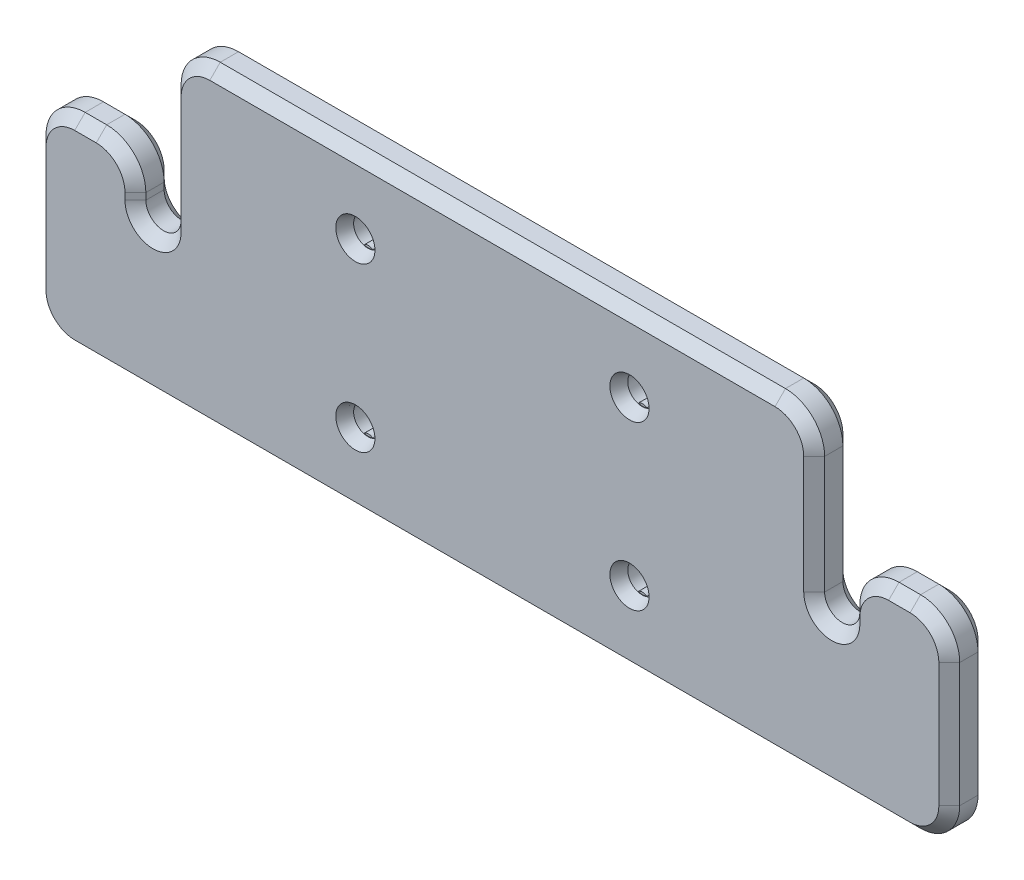
SolidWorks part; units mm, degrees
ref_plane "Front Plane" through (0, 0, 0) normal (0, 0, 1) x (1, 0, 0)
ref_plane "Top Plane" through (0, 0, 0) normal (0, 1, 0) x (1, 0, 0)
ref_plane "Right Plane" through (0, 0, 0) normal (1, 0, 0) x (0, 0, -1)
sketch "Sketch1" plane through (0, 0, 0) normal (0, 0, 1) x (1, 0, 0)
  line L0 (0, 12) -> (0, -12) construction
  line L1 (32, 12) -> (-32, 12)
  line L2 (35, 9) -> (35, -9)
  line L4 (-35, 9) -> (-35, -9)
  line L5 (10.5, 0) -> (-10.5, 0) construction
  line L6 (-10.5, -6.25) -> (-10.5, 6.25) construction
  line L7 (10.5, 6.25) -> (10.5, -6.25) construction
  line L8 (32, -12) -> (-32, -12)
  arc A1 (-32, 12) -> (-35, 9) centre (-32, 9) ccw
  arc A2 (32, 12) -> (35, 9) centre (32, 9) cw
  arc A3 (32, -12) -> (35, -9) centre (32, -9) ccw
  arc A4 (-32, -12) -> (-35, -9) centre (-32, -9) cw
  point P4 (10.5, 6.25)
  point P6 (0, 0)
  point P7 (-10.5, -6.25)
  point P9 (-10.5, 6.25)
  point P17 (-35, -12)
  point P20 (-35, 12)
  dimension "D2" = 3
  dimension "D1" = 70
  dimension "D3" = 24
  dimension "D5" = 21
  dimension "D6" = 12.5
extrude "Boss-Extrude1" add sketch "Sketch1" along normal blind 3
sketch "Sketch4" plane through (0, 0, 0) normal (0, 0, -1) x (-1, 0, 0)
  circle A0 centre (-10.5, 6.25) radius 2.3
  circle A1 centre (10.5, 6.25) radius 2.3
  circle A2 centre (10.5, -6.25) radius 2.3
  circle A3 centre (-10.5, -6.25) radius 2.3
  dimension "D1" = 4.6
extrude "Boss-Extrude2" add sketch "Sketch4" along normal blind 2
hole_wizard "M2 Clearance Hole1" positions "Sketch2" profile "Sketch3" hole size "M2" standard "ISO" end condition through all
sketch "Sketch2" plane through (0, 0, 3) normal (0, 0, 1) x (1, 0, 0)
  point P0 (10.5, 6.25)
  point P2 (10.5, -6.25)
  point P4 (-10.5, -6.25)
  point P6 (-10.5, 6.25)
sketch "Sketch3" plane through (10.5, 6.25, 3) normal (1, 0, 0) x (0, -1, 0)
  line L0 (0, 0) -> (0, 5)
  line L1 (0, 5) -> (1.1, 5)
  line L2 (1.1, 5) -> (1.1, 0.9657)
  line L3 (1.1, 0.9657) -> (1.5, 0)
  line L5 (1.5, 0) -> (0, 0)
  line L6 (-1.1, 0.9657) -> (-1.5, 0) construction
  line L11 (0, -6.35) -> (0, 107.95) construction
  dimension "Thru Hole Dia." = 2.2
  dimension "Thru Hole Depth" = 5
  dimension "Near C'Sink Dia." = 3
  dimension "Near C'Sink Angle" = 45
sketch "Sketch6" plane through (0, 0, 3) normal (0, 0, 1) x (1, 0, 0)
  line L0 (8.0915, 5.15) -> (12.5968, 5.15) construction
  line L1 (8.3943, 5.32) -> (12.5968, 5.32) construction
  line L2 (10.5, 6.25) -> (10.5, -6.25) construction
  line L3 (8.1393, 6.25) -> (12.8607, 6.25) construction
  line L4 (8.3943, 7.18) -> (12.5968, 7.18) construction
  line L5 (8.0915, 7.35) -> (12.5968, 7.35) construction
  line L6 (10.1244, 5.15) -> (10.8756, 5.15)
  line L7 (10.1244, 7.35) -> (10.8756, 7.35)
  line L8 (-10.5, 0) -> (10.5, 0) construction
  line L9 (0, -12) -> (0, 12.0448) construction
  line L11 (10.5, 0) -> (-10.5, 0) construction
  line L12 (-10.5, -6.25) -> (-10.5, 6.25) construction
  line L13 (-10.1244, 5.15) -> (-10.8756, 5.15)
  line L14 (-10.1244, 7.35) -> (-10.8756, 7.35)
  line L15 (10.1244, -7.35) -> (10.8756, -7.35)
  line L16 (10.1244, -5.15) -> (10.8756, -5.15)
  line L17 (-10.1244, -7.35) -> (-10.8756, -7.35)
  line L18 (-10.1244, -5.15) -> (-10.8756, -5.15)
  arc A0 (10.8756, 7.35) -> (10.1244, 7.35) centre (10.5, 7.68) cw
  circle A1 centre (10.5, 6.25) radius 1.1 construction
  arc A2 (10.8756, 5.15) -> (10.1244, 5.15) centre (10.5, 4.82) ccw
  arc A3 (-10.8756, 5.15) -> (-10.1244, 5.15) centre (-10.5, 4.82) cw
  arc A4 (-10.8756, 7.35) -> (-10.1244, 7.35) centre (-10.5, 7.68) ccw
  arc A5 (10.8756, -7.35) -> (10.1244, -7.35) centre (10.5, -7.68) ccw
  arc A6 (10.8756, -5.15) -> (10.1244, -5.15) centre (10.5, -4.82) cw
  arc A7 (-10.8756, -7.35) -> (-10.1244, -7.35) centre (-10.5, -7.68) cw
  arc A8 (-10.8756, -5.15) -> (-10.1244, -5.15) centre (-10.5, -4.82) ccw
  point P25 (10.5, 6.25)
  point P31 (10.5, 5.15)
  dimension "D1" = 1.86
  dimension "D2" = 0.5
extrude "Boss-Extrude3" add sketch "Sketch6" against normal blind 0.75 from offset 1 offset against normal yes
chamfer "Chamfer1" distance 2 distance2 0.4 4 edges at (-12.8, -6.25, -2) (-12.8, 6.25, -2) (8.2, 6.25, -2) (8.2, -6.25, -2) first distance on face at (-12.8, -6.25, -2) first distance on face at (-12.8, 6.25, -2) first distance on face at (8.2, 6.25, -2) first distance on face at (8.2, -6.25, -2)
sketch "Sketch5" plane through (0, 0, -2) normal (0, 0, -1) x (-1, 0, 0)
  line L0 (8.7126, 7.6974) -> (10.5, 6.25)
  line L1 (10.5, 6.25) -> (9.1808, 4.366)
  line L2 (10.4197, -8.5486) -> (10.5, -6.25)
  line L3 (10.5, -6.25) -> (8.2589, -6.7674)
  line L4 (-12.6747, 5.5012) -> (-10.5, 6.25)
  line L5 (-10.5, 6.25) -> (-10.7404, 3.9626)
  line L6 (-10.5, -3.95) -> (-10.5, -6.25)
  line L7 (-10.5, -6.25) -> (-8.2004, -6.2099)
  line L8 (-10.5, 6.25) -> (-10.5, -6.25) construction
  line L9 (10.5, 6.25) -> (10.5, -6.25) construction
  arc A0 (8.7126, 7.6974) -> (9.1808, 4.366) centre (10.5, 6.25) ccw
  circle A1 centre (10.5, 6.25) radius 2.3 construction
  arc A2 (8.2589, -6.7674) -> (10.4197, -8.5486) centre (10.5, -6.25) ccw
  circle A3 centre (10.5, -6.25) radius 2.3 construction
  arc A4 (-10.5, -3.95) -> (-8.2004, -6.2099) centre (-10.5, -6.25) cw
  circle A5 centre (-10.5, -6.25) radius 2.3 construction
  arc A6 (-12.6747, 5.5012) -> (-10.7404, 3.9626) centre (-10.5, 6.25) ccw
  circle A7 centre (-10.5, 6.25) radius 2.3 construction
  dimension "D1" = 35
  dimension "D2" = 94
  dimension "D3" = 103
  dimension "D4" = 75
  dimension "D5" = 6
  dimension "D6" = 65
  dimension "D7" = 89
extrude "Cut-Extrude2" cut sketch "Sketch5" against normal blind 0.8
sketch "Sketch7" plane through (0, 0, 3) normal (0, 0, 1) x (1, 0, 0)
  line L0 (26, -12) -> (26, 12) construction
  line L1 (32, -12) -> (-32, -12) construction
  line L2 (32, 12) -> (-32, 12) construction
  line L3 (35, 3.5) -> (27.35, 3.5)
  line L4 (35, 9) -> (35, -9) construction
  line L5 (24.65, 12) -> (24.65, 0)
  line L6 (27.35, 3.5) -> (27.35, 0)
  line L7 (35, 3.5) -> (35, 12)
  line L8 (35, 12) -> (24.65, 12)
  line L9 (0, -12) -> (0, 11.9047) construction
  line L10 (-35, 12) -> (-24.65, 12)
  line L11 (-35, 3.5) -> (-35, 12)
  line L12 (-27.35, 3.5) -> (-27.35, 0)
  line L13 (-24.65, 12) -> (-24.65, 0)
  line L14 (-35, 3.5) -> (-27.35, 3.5)
  arc A0 (24.65, 0) -> (27.35, 0) centre (26, 0) ccw
  arc A1 (-24.65, 0) -> (-27.35, 0) centre (-26, 0) cw
  circle A2 centre (26, 0) radius 5 construction
  dimension "D1" = 1.35
  dimension "D3" = 3.5
extrude "Cut-Extrude3" cut sketch "Sketch7" against normal through all
fillet "Fillet1" radius 3 6 edges at (-35, 3.5, 1.5) (-27.35, 3.5, 1.5) (-24.65, 12, 1.5) (24.65, 12, 1.5) (27.35, 3.5, 1.5) (35, 3.5, 1.5)
chamfer "Chamfer2" distance 0.8 angle 45 40 edges at (0, 12, 0) (-23.7713, 11.1213, 0) (23.7713, 11.1213, 0) (-24.65, 4.5, 0) (24.65, 4.5, 0) (-26, -1.35, 0) (26, -1.35, 0) (-27.35, 0.25, 0) (27.35, 0.25, 0) (-28.2287, 2.6213, 0) (28.2287, 2.6213, 0) (-31.175, 3.5, 0) (31.175, 3.5, 0) (-34.1213, 2.6213, 0) (34.1213, 2.6213, 0) (-35, -4.25, 0) (35, -4.25, 0) (-34.1213, -11.1213, 0) (34.1213, -11.1213, 0) (0, -12, 0) (0, 12, 3) (-23.7713, 11.1213, 3) (23.7713, 11.1213, 3) (-24.65, 4.5, 3) (24.65, 4.5, 3) (-26, -1.35, 3) (26, -1.35, 3) (-27.35, 0.25, 3) (27.35, 0.25, 3) (-28.2287, 2.6213, 3) (28.2287, 2.6213, 3) (-31.175, 3.5, 3) (31.175, 3.5, 3) (-34.1213, 2.6213, 3) (34.1213, 2.6213, 3) (-35, -4.25, 3) (35, -4.25, 3) (-34.1213, -11.1213, 3) (34.1213, -11.1213, 3) (0, -12, 3)
